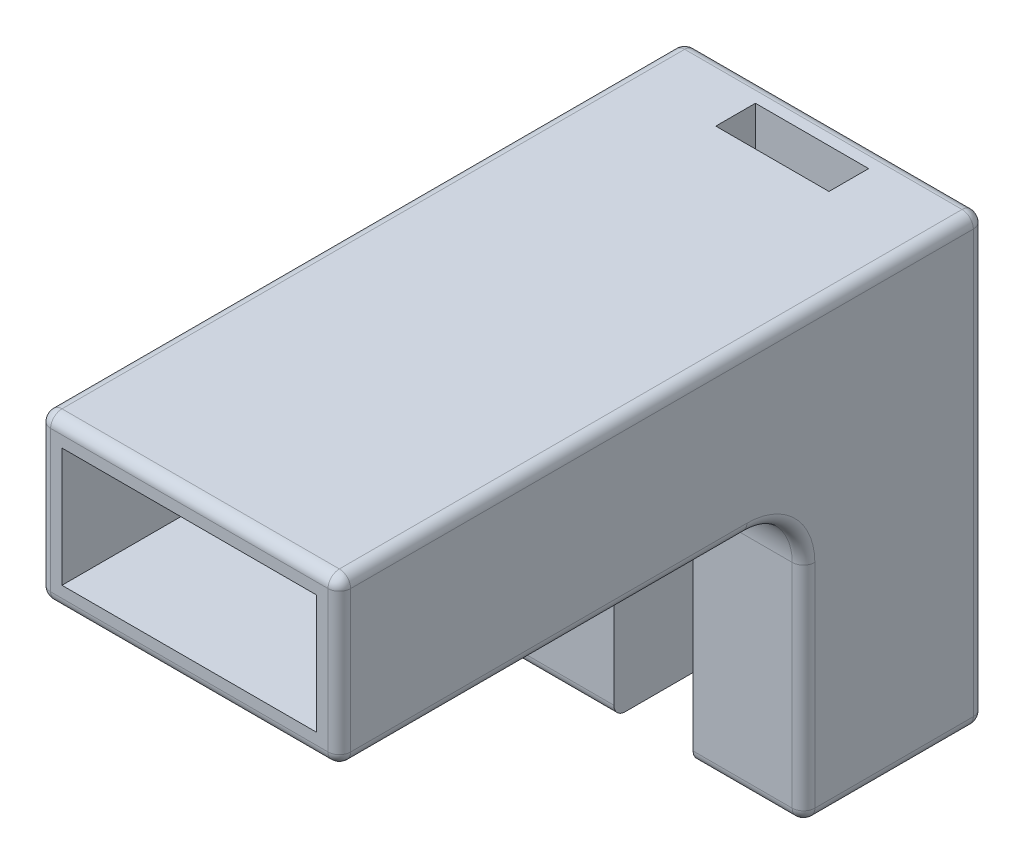
SolidWorks part; units mm, degrees
ref_plane "正面" through (0, 0, 0) normal (0, 0, 1) x (1, 0, 0)
ref_plane "平面" through (0, 0, 0) normal (0, 1, 0) x (1, 0, 0)
ref_plane "右側面" through (0, 0, 0) normal (1, 0, 0) x (0, 0, -1)
sketch "ｽｹｯﾁ2" plane through (0, 0, 0) normal (0, 0, 1) x (1, 0, 0)
  line L1 (0, 0) -> (26.5, 0)
  line L2 (0, 0) -> (0, 14.5)
  line L3 (0, 14.5) -> (26.5, 14.5)
  line L4 (26.5, 0) -> (26.5, 14.5)
  dimension "D1" = 14.5
  dimension "D2" = 26.5
extrude "ﾎﾞｽ - 押し出し1" add sketch "ｽｹｯﾁ2" along normal blind 57
sketch "ｽｹｯﾁ6" plane through (0, 0, 57) normal (0, 0, 1) x (1, 0, 0)
  line L0 (26.5, 14.5) -> (0, 14.5) construction
  line L1 (2, 12.5) -> (24.5, 12.5)
  line L2 (2, 12.5) -> (2, 2)
  line L3 (2, 2) -> (24.5, 2)
  line L4 (24.5, 12.5) -> (24.5, 2)
  line L5 (0, 14.5) -> (0, 0) construction
  dimension "D1" = 10.5
  dimension "D2" = 22.5
  dimension "D3" = 2
  dimension "D4" = 2
extrude "ｶｯﾄ - 押し出し1" cut sketch "ｽｹｯﾁ6" against normal blind 49
sketch "ｽｹｯﾁ7" plane through (0, 0, 0) normal (0, -1, 0) x (1, 0, 0)
  line L0 (26.5, 57) -> (26.5, 0) construction
  line L1 (0, 0) -> (26.5, 0)
  line L2 (0, 0) -> (0, 16)
  line L3 (0, 16) -> (26.5, 16)
  line L4 (26.5, 0) -> (26.5, 16)
  dimension "D1" = 16
extrude "ﾎﾞｽ - 押し出し2" add sketch "ｽｹｯﾁ7" along normal blind 24.8
fillet "ﾌｨﾚｯﾄ1" radius 5 1 edges at (13.25, 0, 16)
fillet "ﾌｨﾚｯﾄ2" radius 1 1 edges at (26.5, 14.5, 28.5)
fillet "ﾌｨﾚｯﾄ4" radius 1 7 edges at (12.75, 14.5, 0) (26.2071, 14.2071, 0) (26.5, -5.65, 0) (26.5, -24.8, 8) (26.5, -14.9, 16) (26.5, -1.4645, 17.4645) (26.5, 0, 39)
fillet "ﾌｨﾚｯﾄ5" radius 1 11 edges at (0, 14.2071, 0.2929) (26.2071, -24.5071, 0.2929) (26.2071, -24.5071, 15.7071) (0, 14.5, 29) (0, -5.65, 0) (0, 0, 39) (0, -1.4645, 17.4645) (0, -14.9, 16) (0, -24.8, 8) (12.75, -24.8, 0) (12.75, -24.8, 16)
fillet "ﾌｨﾚｯﾄ6" radius 1 8 edges at (26.2071, 0.2929, 57) (26.2071, 14.2071, 57) (0.2929, 14.2071, 57) (0.2929, 0.2929, 57) (26.5, 7.25, 57) (13.25, 14.5, 57) (13.25, 0, 57) (0, 7.25, 57)
sketch "ｽｹｯﾁ8" plane through (0, -24.8, 0) normal (0, -1, 0) x (1, 0, 0)
  line L0 (1, 16) -> (25.5, 16) construction
  line L1 (9.75, 16) -> (16.75, 16)
  line L2 (9.75, 16) -> (9.75, 6.5)
  line L4 (16.75, 16) -> (16.75, 6.5)
  line L5 (11.25, 6.5) -> (11.25, 5.5)
  line L6 (11.25, 5.5) -> (8.25, 5.5)
  line L7 (13.25, 16) -> (13.25, 2) construction
  line L8 (0, 1) -> (0, 15) construction
  line L9 (8.25, 5.5) -> (8.25, 2)
  line L10 (8.25, 2) -> (18.25, 2)
  line L11 (18.25, 2) -> (18.25, 5.5)
  line L12 (18.25, 5.5) -> (15.25, 5.5)
  line L13 (15.25, 5.5) -> (15.25, 6.5)
  line L14 (9.75, 6.5) -> (11.25, 6.5)
  line L15 (15.25, 6.5) -> (16.75, 6.5)
  line L16 (25.5, 0) -> (1, 0) construction
  point P13 (13.2645, 0)
  dimension "D1" = 9.5
  dimension "D2" = 7
  dimension "D3" = 13.25
  dimension "D4" = 3.5
  dimension "D5" = 4
  dimension "D6" = 2
  dimension "D7" = 1
  dimension "D8" = 3.5
  dimension "D9" = 2
  dimension "D10" = 10
extrude "ｶｯﾄ - 押し出し2" cut sketch "ｽｹｯﾁ8" against normal blind 20
sketch "ｽｹｯﾁ10" plane through (0, -24.8, 0) normal (0, -1, 0) x (1, 0, 0)
  line L1 (8.25, 5.5) -> (18.25, 5.5)
  line L2 (8.25, 5.5) -> (8.25, 2)
  line L3 (8.25, 2) -> (18.25, 2)
  line L4 (18.25, 5.5) -> (18.25, 2)
extrude "ｶｯﾄ - 押し出し3" cut sketch "ｽｹｯﾁ10" against normal blind 40
